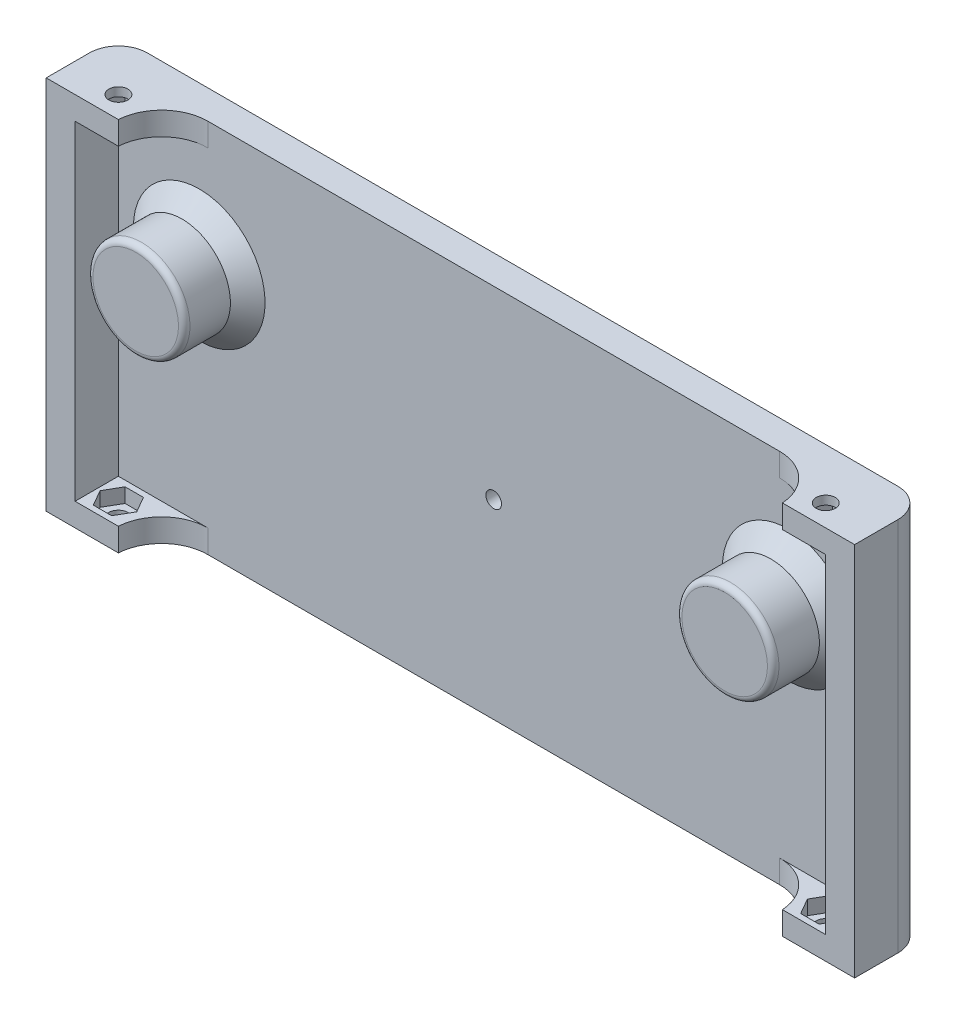
SolidWorks part; units mm, degrees
ref_plane "Front Plane" through (0, 0, 0) normal (0, 0, 1) x (1, 0, 0)
ref_plane "Top Plane" through (0, 0, 0) normal (0, 1, 0) x (1, 0, 0)
ref_plane "Right Plane" through (0, 0, 0) normal (1, 0, 0) x (0, 0, -1)
sketch "Sketch1" plane through (0, 0, 0) normal (0, 0, 1) x (1, 0, 0)
  line L1 (0, 0) -> (140, 0)
  line L2 (0, 0) -> (0, 65)
  line L3 (0, 65) -> (140, 65)
  line L4 (140, 0) -> (140, 65)
  dimension "D1" = 65
  dimension "D2" = 140
extrude "Boss-Extrude1" add sketch "Sketch1" along normal blind 12.5
sketch "Sketch3" plane through (0, 65, 0) normal (0, 1, 0) x (1, 0, 0)
  line L0 (5, -12.5) -> (135, -12.5)
  line L9 (135, -5) -> (135, -12.5)
  line L10 (5, -5) -> (135, -5)
  line L11 (5, -12.5) -> (5, -5)
  line L12 (135, -5) -> (135, -12.5)
  line L13 (5, -5) -> (135, -5)
  line L14 (5, -12.5) -> (5, -5)
  dimension "D1" = 5
extrude "Cut-Extrude1" cut sketch "Sketch3" against normal through all
fillet "Fillet1" radius 5 2 edges at (140, 32.5, 0) (0, 32.5, 0)
sketch "Sketch4" plane through (0, 0, 0) normal (0, -1, 0) x (1, 0, 0)
  line L0 (135, 5) -> (5, 5) construction
  line L1 (5, 12.5) -> (12.5, 12.5)
  line L2 (5, 12.5) -> (5, 5)
  line L3 (5, 5) -> (12.5, 5)
  line L4 (12.5, 12.5) -> (12.5, 5)
  line L6 (135, 5) -> (127.5, 5)
  line L7 (135, 5) -> (135, 12.5)
  line L8 (135, 12.5) -> (127.5, 12.5)
  line L9 (127.5, 5) -> (127.5, 12.5)
extrude "Boss-Extrude2" add sketch "Sketch4" against normal blind 4
sketch "Sketch5" plane through (0, 4, 0) normal (0, 1, 0) x (1, 0, 0)
  line L0 (131.25, -5) -> (131.25, -12.5) construction
  line L1 (127.5, -5) -> (135, -5) construction
  line L2 (135, -12.5) -> (127.5, -12.5) construction
  line L3 (70, 0) -> (70, -12.5) construction
  line L4 (134.4254, -8.75) -> (132.8377, -6)
  line L5 (132.8377, -6) -> (129.6623, -6)
  line L6 (129.6623, -6) -> (128.0746, -8.75)
  line L7 (128.0746, -8.75) -> (129.6623, -11.5)
  line L8 (129.6623, -11.5) -> (132.8377, -11.5)
  line L9 (132.8377, -11.5) -> (134.4254, -8.75)
  line L10 (135, 0) -> (5, 0) construction
  line L11 (10.3377, -6) -> (11.9254, -8.75)
  line L12 (11.9254, -8.75) -> (10.3377, -11.5)
  line L13 (7.1623, -11.5) -> (5.5746, -8.75)
  line L14 (10.3377, -11.5) -> (7.1623, -11.5)
  line L15 (7.1623, -6) -> (10.3377, -6)
  line L16 (5.5746, -8.75) -> (7.1623, -6)
  circle A0 centre (131.25, -8.75) radius 2.75 construction
  circle A1 centre (131.25, -8.75) radius 1.65
  circle A2 centre (8.75, -8.75) radius 1.65
  dimension "D2" = 3.3
  dimension "D1" = 5.5
extrude "Cut-Extrude2" cut sketch "Sketch5" against normal blind 2.5
extrude "Cut-Extrude3" cut sketch "Sketch5<3>" against normal through all contours A2 | A1 region at (131.25, 4, 8.75) region at (8.75, 4, 8.75)
sketch "Sketch5<3>" plane through (0, 4, 0) normal (0, 1, 0) x (1, 0, 0) same geometry as "Sketch5"
fillet "Fillet2" radius 8 2 edges at (127.5, 2, 5) (12.5, 2, 5)
ref_plane "Plane1" through (0, 32.5, 0) normal (0, 1, 0) x (1, 0, 0)
mirror "Mirror1" about plane through (0, 32.5, 0) normal (0, 1, 0) of "Cut-Extrude3", "Cut-Extrude2", "Boss-Extrude2", "Fillet2"
sketch "Sketch7" plane through (0, 0, 5) normal (0, 0, 1) x (1, 0, 0)
  line L0 (140, 0) -> (121, 0) construction
  line L1 (119.5156, 0) -> (20.4844, 0) construction
  line L2 (121, 0) -> (121, 42.7) construction
  line L3 (70, 65) -> (70, 0) construction
  line L4 (119.5156, 65) -> (20.4844, 65) construction
  circle A0 centre (121, 42.7) radius 8.4
  circle A1 centre (19, 42.7) radius 8.4
  dimension "D3" = 16.8
  dimension "D1" = 19
  dimension "D2" = 42.7
extrude "Boss-Extrude3" add sketch "Sketch7" along normal blind 11
fillet "Fillet3" radius 1 2 edges at (129.4, 42.7, 16) (10.6, 42.7, 16)
chamfer "Chamfer1" distance 3 angle 45 2 edges at (112.6, 42.7, 5) (10.6, 42.7, 5)
sketch "Sketch8" plane through (0, 0, 0) normal (0, 0, -1) x (-1, 0, 0)
  line L0 (-70, 65) -> (-70, 33) construction
  line L1 (-135, 65) -> (-5, 65) construction
  circle A0 centre (-70, 33) radius 1.35
  dimension "D2" = 2.7
  dimension "D1" = 32
extrude "Cut-Extrude4" cut sketch "Sketch8" against normal through all
